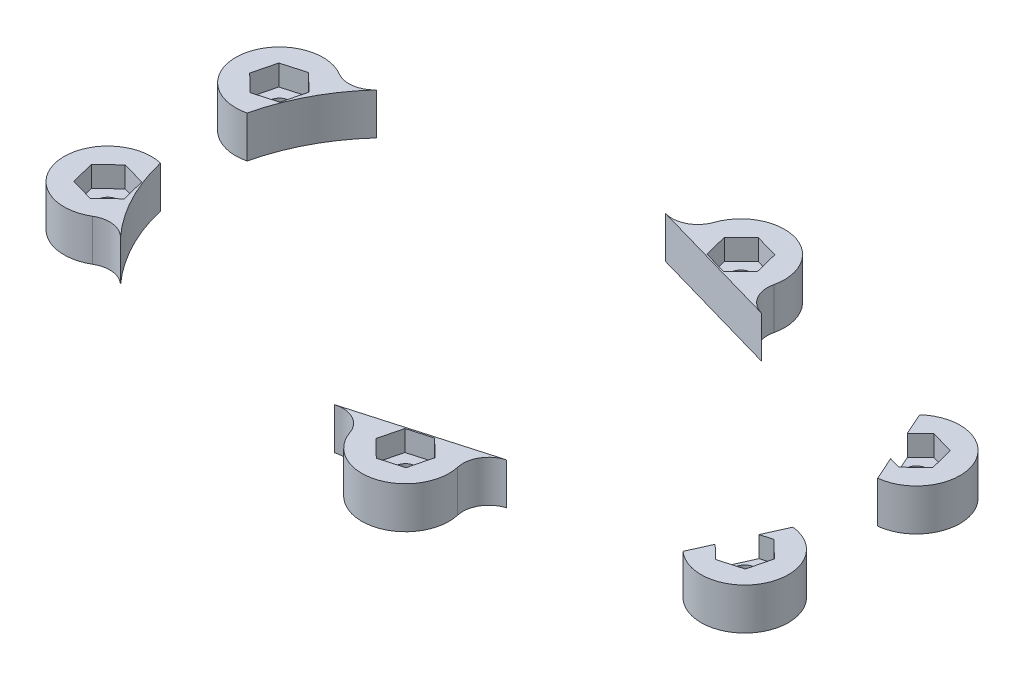
SolidWorks part; units mm, degrees
ref_plane "Front Plane" through (0, 0, 0) normal (0, 0, 1) x (1, 0, 0)
ref_plane "Top Plane" through (0, 0, 0) normal (0, 1, 0) x (1, 0, 0)
ref_plane "Right Plane" through (0, 0, 0) normal (1, 0, 0) x (0, 0, -1)
sketch "Sketch1" plane through (0, 0, 0) normal (0, 1, 0) x (1, 0, 0)
  line L0 (0, 73.0538) -> (0, -65.1274) construction
  line L1 (35.5, 6.365) -> (-28.5632, 24.502) construction
  line L2 (-70.6215, 0) -> (67.3742, 0) construction
  line L3 (35.5, -6.365) -> (-28.5632, -24.502) construction
  line L4 (4.5177, -15.1364) -> (0.1592, 0.2585)
  line L5 (0.1592, 0.2585) -> (4.6815, 1.5388)
  line L6 (4.6815, 1.5388) -> (9.04, -13.8561)
  line L7 (9.04, -13.8561) -> (9.5848, -15.7805)
  line L8 (9.5848, -15.7805) -> (5.0625, -17.0608)
  line L9 (5.0625, -17.0608) -> (4.5177, -15.1364)
  line L10 (-35.5, 0) -> (-60.5, 0) construction
  line L11 (-35.5, 0) -> (-35.5, 25) construction
  line L13 (-100, -75) -> (100, -75)
  line L14 (-100, -75) -> (-100, 75)
  line L15 (-100, 75) -> (100, 75)
  line L16 (100, -75) -> (100, 75)
  line L17 (-100, -75) -> (100, 75) construction
  line L18 (-100, 75) -> (100, -75) construction
  circle A0 centre (35.5, 0) radius 6
  circle A1 centre (-35.5, 0) radius 13.5
  circle A2 centre (-35.5, 0) radius 25.465 construction
  circle A3 centre (35.5, 0) radius 6.365 construction
  circle A4 centre (-60.5, 0) radius 2
  circle A5 centre (-35.5, 25) radius 2
  circle A6 centre (-10.5, 0) radius 2
  circle A7 centre (-35.5, -25) radius 2
  circle A8 centre (35.5, 18.5) radius 2.5
  circle A9 centre (35.5, -18.5) radius 2.5
  point P35 (0, 0)
  dimension "D1" = 12
  dimension "D2" = 27
  dimension "D5" = 50.93
  dimension "D6" = 12.73
  dimension "D12" = 4
  dimension "D19" = 5
  dimension "D3" = 71
  dimension "D4" = 35.5
  dimension "D7" = 90
  dimension "D8" = 27.5
  dimension "D9" = 4.7
  dimension "D10" = 16
  dimension "D11" = 2
  dimension "D13" = 25
  dimension "D15" = 90
  dimension "D16" = 25
  dimension "D17" = 200
  dimension "D18" = 150
  dimension "D20" = 18.5
  dimension "D14" = 4
extrude "Boss-Extrude1" add sketch "Sketch1" along normal blind 4
sketch "Sketch3" plane through (0, 4, 0) normal (0, 1, 0) x (1, 0, 0)
  line L0 (-26.5739, 31.2502) -> (39.0704, 12.5001)
  line L1 (-100, -75) -> (100, -75)
  line L2 (-100, -75) -> (-100, 75)
  line L3 (-100, 75) -> (100, 75)
  line L4 (100, -75) -> (100, 75)
  line L5 (-35.5, 0) -> (35.5, 0) construction
  line L6 (-26.5739, -31.2502) -> (39.0704, -12.5001)
  arc A0 (-26.5739, 31.2502) -> (-26.5739, -31.2502) centre (-35.5, 0) ccw
  arc A1 (39.0704, -12.5001) -> (39.0704, 12.5001) centre (35.5, 0) ccw
  dimension "D1" = 65
  dimension "D2" = 26
extrude "Boss-Extrude2" add sketch "Sketch3" along normal blind 8.25
sketch "Sketch6" plane through (0, 12.25, 0) normal (0, 1, 0) x (1, 0, 0)
  circle A0 centre (35.5, 18.5) radius 5.4
  circle A1 centre (35.5, -18.5) radius 5.4
  dimension "D1" = 10.8
extrude "Cut-Extrude2" cut sketch "Sketch6" against normal up to surface (8.25 mm away) up to face at (-35.5, 4, 27)
fillet "Fillet1" radius 2.5 4 edges at (9.5848, 2, 15.7805) (5.0625, 2, 17.0608) (4.6815, 2, -1.5388) (0.1592, 2, -0.2585)
fillet "Fillet2" radius 5 4 edges at (36.5847, 8.125, 13.2101) (31.7849, 8.125, 14.5811) (36.5847, 8.125, -13.2101) (31.7849, 8.125, -14.5811)
sketch "Sketch2" plane through (0, 4, 0) normal (0, 1, 0) x (1, 0, 0)
  line L0 (29.5, 0) -> (41.5, 0) construction
  line L1 (35.5, 0) -> (35.5, -6) construction
  line L2 (35.5, 0) -> (35.5, 6) construction
  circle A0 centre (-35.5, 25) radius 4.4
  circle A1 centre (-10.5, 0) radius 4.4
  circle A2 centre (-35.5, -25) radius 4.4
  circle A3 centre (-60.5, 0) radius 4.4
  circle A4 centre (35.5, 0) radius 6 construction
  circle A7 centre (35.5, 18.5) radius 5.4
  circle A8 centre (35.5, -18.5) radius 5.4
  arc A9 (40.6003, 16.7261) -> (30.3389, 20.0883) centre (35.5, 18.5) ccw construction
  dimension "D1" = 8.8
extrude "Cut-Extrude1" cut sketch "Sketch2" against normal blind 2
sketch "Sketch8" plane through (0, 0, 0) normal (0, -1, 0) x (1, 0, 0)
  line L0 (-35.5, 0) -> (-100, 0) construction
  line L1 (-100, -75) -> (-100, 75) construction
  line L2 (-35.5, 0) -> (100, 0) construction
  line L3 (100, 75) -> (100, -75) construction
  line L4 (49.5, 21.4955) -> (49.5, -20.5045) construction
  line L5 (0, 32.8542) -> (0, -34.16) construction
  line L6 (-73, 27.0496) -> (-73, -26.9504) construction
  line L11 (-26.5739, -31.2502) -> (24.1868, -16.7513)
  line L12 (24.1868, 16.7513) -> (-26.5739, 31.2502)
  line L13 (-26.5739, -31.2502) -> (24.1868, -16.7513) construction
  line L14 (24.1868, 16.7513) -> (-26.5739, 31.2502) construction
  circle A0 centre (-35.5, 0) radius 32.5 construction
  arc A1 (-26.5739, 31.2502) -> (-26.5739, -31.2502) centre (-35.5, 0) ccw construction
  circle A13 centre (49.5, 16.5) radius 2
  circle A14 centre (-73, 16.5) radius 2
  circle A15 centre (0, 32.25) radius 2
  circle A16 centre (49.5, 16.5) radius 4.4 construction
  circle A17 centre (0, 32.25) radius 4.4 construction
  circle A18 centre (-73, 16.5) radius 4.4 construction
  circle A19 centre (35.5, 18.5) radius 5.4 construction
  arc A20 (40.6003, 16.7261) -> (30.3389, 20.0883) centre (35.5, 18.5) ccw construction
  circle A21 centre (35.5, -18.5) radius 5.4 construction
  circle A22 centre (-73, -16.5) radius 4.4 construction
  circle A23 centre (-73, -16.5) radius 2
  circle A24 centre (0, -32.25) radius 4.4 construction
  circle A25 centre (0, -32.25) radius 2
  circle A26 centre (49.5, -16.5) radius 4.4 construction
  circle A27 centre (49.5, -16.5) radius 2
  circle A28 centre (49.5, 16.5) radius 8.4 construction
  circle A29 centre (0, 32.25) radius 8.4 construction
  circle A30 centre (-73, 16.5) radius 8.4 construction
  arc A44 (30.3389, -20.0883) -> (40.6003, -16.7261) centre (35.5, -18.5) ccw
  arc A45 (42.5943, -10.8936) -> (40.6003, -16.7261) centre (45.3228, -15.0835) ccw
  arc A46 (42.5943, -10.8936) -> (42.5943, 10.8936) centre (35.5, 0) ccw
  arc A47 (40.6003, 16.7261) -> (42.5943, 10.8936) centre (45.3228, 15.0835) ccw
  arc A48 (30.3389, -20.0883) -> (24.1868, -16.7513) centre (25.5601, -21.559) ccw
  arc A49 (40.6003, 16.7261) -> (30.3389, 20.0883) centre (35.5, 18.5) ccw
  arc A50 (24.1868, 16.7513) -> (30.3389, 20.0883) centre (25.5601, 21.559) ccw
  arc A51 (-26.5739, 31.2502) -> (-26.5739, -31.2502) centre (-35.5, 0) ccw
  arc A52 (30.3389, -20.0883) -> (40.6003, -16.7261) centre (35.5, -18.5) ccw construction
  arc A53 (42.5943, -10.8936) -> (40.6003, -16.7261) centre (45.3228, -15.0835) ccw construction
  arc A54 (42.5943, -10.8936) -> (42.5943, 10.8936) centre (35.5, 0) ccw construction
  arc A55 (40.6003, 16.7261) -> (42.5943, 10.8936) centre (45.3228, 15.0835) ccw construction
  arc A56 (30.3389, -20.0883) -> (24.1868, -16.7513) centre (25.5601, -21.559) ccw construction
  arc A57 (40.6003, 16.7261) -> (30.3389, 20.0883) centre (35.5, 18.5) ccw construction
  arc A58 (24.1868, 16.7513) -> (30.3389, 20.0883) centre (25.5601, 21.559) ccw construction
  arc A59 (-26.5739, 31.2502) -> (-26.5739, -31.2502) centre (-35.5, 0) ccw construction
  dimension "D1" = 0
  dimension "D2" = 4
  dimension "D4" = 33
  dimension "D5" = 49.5
  dimension "D3" = 8.8
  dimension "D8" = 16.8
  dimension "D6" = 64.5
  dimension "D7" = 73
extrude "Cut-Extrude3" cut sketch "Sketch8" against normal through all both and the other way through all
sketch "Sketch13" plane through (0, 12.25, 0) normal (0, 1, 0) x (1, 0, 0)
  line L0 (-100, 0) -> (100, 0) construction
  line L1 (-100, 75) -> (-100, -75) construction
  line L2 (100, -75) -> (100, 75) construction
  line L5 (-8.1313, 30.1424) -> (-25.4754, 35.0964)
  line L6 (5.7914, -26.1656) -> (25.2854, -20.5975)
  line L7 (-25.4754, -35.0964) -> (25.2854, -20.5975)
  line L8 (25.2854, 20.5975) -> (-25.4754, 35.0964)
  line L9 (-25.4754, -35.0964) -> (-8.1313, -30.1424)
  line L10 (25.2854, 20.5975) -> (5.7914, 26.1656)
  arc A0 (5.7914, 26.1656) -> (-8.1313, 30.1424) centre (0, 32.25) ccw
  arc A1 (50.4188, 8.1504) -> (43.8854, 22.7479) centre (49.5, 16.5) ccw
  arc A2 (-65.6518, 20.5699) -> (-71.0361, 8.3328) centre (-73, 16.5) ccw
  arc A3 (-65.6518, -20.5699) -> (-71.0361, -8.3328) centre (-73, -16.5) cw
  arc A4 (5.7914, -26.1656) -> (-8.1313, -30.1424) centre (0, -32.25) cw
  arc A5 (50.4188, -8.1504) -> (43.8854, -22.7479) centre (49.5, -16.5) cw
  arc A14 (-71.0361, 8.3328) -> (-71.0361, -8.3328) centre (-35.5, 0) ccw
  arc A15 (-65.6518, -20.5699) -> (-25.4754, -35.0964) centre (-35.5, 0) ccw
  arc A22 (44.3783, 15.412) -> (26.5158, 21.2649) centre (35.5, 18.5) ccw
  arc A23 (44.3783, 15.412) -> (44.7771, 14.2455) centre (45.3228, 15.0835) ccw
  arc A24 (44.7771, -14.2455) -> (44.7771, 14.2455) centre (35.5, 0) ccw
  arc A25 (44.7771, -14.2455) -> (44.3783, -15.412) centre (45.3228, -15.0835) ccw
  arc A26 (26.5158, -21.2649) -> (44.3783, -15.412) centre (35.5, -18.5) ccw
  arc A27 (26.5158, -21.2649) -> (25.2854, -20.5975) centre (25.5601, -21.559) ccw
  arc A28 (-25.4754, 35.0964) -> (-25.4754, -35.0964) centre (-35.5, 0) ccw
  arc A29 (25.2854, 20.5975) -> (26.5158, 21.2649) centre (25.5601, 21.559) ccw
  arc A30 (43.8854, 22.7479) -> (26.5158, 21.2649) centre (35.5, 18.5) ccw
  arc A32 (50.4188, -8.1504) -> (50.4188, 8.1504) centre (35.5, 0) ccw
  arc A34 (26.5158, -21.2649) -> (43.8854, -22.7479) centre (35.5, -18.5) ccw
  arc A35 (26.5158, -21.2649) -> (25.2854, -20.5975) centre (25.5601, -21.559) ccw
  arc A36 (-25.4754, 35.0964) -> (-65.6518, 20.5699) centre (-35.5, 0) ccw
  arc A37 (25.2854, 20.5975) -> (26.5158, 21.2649) centre (25.5601, 21.559) ccw
  dimension "D1" = 16.8
  dimension "D2" = 4
extrude "Cut-Extrude6" cut sketch "Sketch13" against normal through all both and the other way through all flip side to cut
fillet "Fillet4" radius 5 6 edges at (-65.6518, 6.125, 20.5699) (-65.6518, 6.125, -20.5699) (-8.1313, 6.125, -30.1424) (5.7914, 6.125, -26.1656) (5.7914, 6.125, 26.1656) (-8.1313, 6.125, 30.1424)
sketch "Sketch16" plane through (0, 12.25, 0) normal (0, 1, 0) x (1, 0, 0)
  line L12 (-25.4754, -35.0964) -> (-14.035, -31.8287)
  line L13 (11.6951, -24.4793) -> (25.2854, -20.5975)
  line L14 (25.2854, 20.5975) -> (11.6951, 24.4793)
  line L15 (-14.035, 31.8287) -> (-25.4754, 35.0964)
  line L16 (-25.4754, -35.0964) -> (-14.035, -31.8287)
  line L17 (11.6951, -24.4793) -> (25.2854, -20.5975)
  line L18 (25.2854, 20.5975) -> (11.6951, 24.4793)
  line L19 (-14.035, 31.8287) -> (-25.4754, 35.0964)
  arc A60 (-71.0361, 8.3328) -> (-71.0361, -8.3328) centre (-35.5, 0) ccw
  arc A61 (-71.0361, -8.3328) -> (-68.692, -23.7112) centre (-73, -16.5) ccw
  arc A62 (-62.4376, -24.6296) -> (-68.692, -23.7112) centre (-66.1277, -28.0035) ccw
  arc A63 (-62.4376, -24.6296) -> (-25.4754, -35.0964) centre (-35.5, 0) ccw
  arc A64 (-7.9372, -34.9997) -> (-14.035, -31.8287) centre (-12.6617, -36.6364) ccw
  arc A65 (-7.9372, -34.9997) -> (8.1921, -30.3926) centre (0, -32.25) ccw
  arc A66 (11.6951, -24.4793) -> (8.1921, -30.3926) centre (13.0683, -29.2871) ccw
  arc A67 (26.5158, -21.2649) -> (25.2854, -20.5975) centre (25.5601, -21.559) ccw
  arc A68 (26.5158, -21.2649) -> (43.8854, -22.7479) centre (35.5, -18.5) ccw
  arc A69 (43.8854, -22.7479) -> (50.4188, -8.1504) centre (49.5, -16.5) ccw
  arc A70 (50.4188, -8.1504) -> (50.4188, 8.1504) centre (35.5, 0) ccw
  arc A71 (50.4188, 8.1504) -> (43.8854, 22.7479) centre (49.5, 16.5) ccw
  arc A72 (43.8854, 22.7479) -> (26.5158, 21.2649) centre (35.5, 18.5) ccw
  arc A73 (25.2854, 20.5975) -> (26.5158, 21.2649) centre (25.5601, 21.559) ccw
  arc A74 (8.1921, 30.3926) -> (11.6951, 24.4793) centre (13.0683, 29.2871) ccw
  arc A75 (8.1921, 30.3926) -> (-7.9372, 34.9997) centre (0, 32.25) ccw
  arc A76 (-14.035, 31.8287) -> (-7.9372, 34.9997) centre (-12.6617, 36.6364) ccw
  arc A77 (-25.4754, 35.0964) -> (-62.4376, 24.6296) centre (-35.5, 0) ccw
  arc A78 (-68.692, 23.7112) -> (-62.4376, 24.6296) centre (-66.1277, 28.0035) ccw
  arc A79 (-68.692, 23.7112) -> (-71.0361, 8.3328) centre (-73, 16.5) ccw
  arc A80 (-71.0361, 8.3328) -> (-71.0361, -8.3328) centre (-35.5, 0) ccw
  arc A81 (-71.0361, -8.3328) -> (-68.692, -23.7112) centre (-73, -16.5) ccw
  arc A82 (-62.4376, -24.6296) -> (-68.692, -23.7112) centre (-66.1277, -28.0035) ccw
  arc A83 (-62.4376, -24.6296) -> (-25.4754, -35.0964) centre (-35.5, 0) ccw
  arc A84 (-7.9372, -34.9997) -> (-14.035, -31.8287) centre (-12.6617, -36.6364) ccw
  arc A85 (-7.9372, -34.9997) -> (8.1921, -30.3926) centre (0, -32.25) ccw
  arc A86 (11.6951, -24.4793) -> (8.1921, -30.3926) centre (13.0683, -29.2871) ccw
  arc A87 (26.5158, -21.2649) -> (25.2854, -20.5975) centre (25.5601, -21.559) ccw
  arc A88 (26.5158, -21.2649) -> (43.8854, -22.7479) centre (35.5, -18.5) ccw
  arc A89 (43.8854, -22.7479) -> (50.4188, -8.1504) centre (49.5, -16.5) ccw
  arc A90 (50.4188, -8.1504) -> (50.4188, 8.1504) centre (35.5, 0) ccw
  arc A91 (50.4188, 8.1504) -> (43.8854, 22.7479) centre (49.5, 16.5) ccw
  arc A92 (43.8854, 22.7479) -> (26.5158, 21.2649) centre (35.5, 18.5) ccw
  arc A93 (25.2854, 20.5975) -> (26.5158, 21.2649) centre (25.5601, 21.559) ccw
  arc A94 (8.1921, 30.3926) -> (11.6951, 24.4793) centre (13.0683, 29.2871) ccw
  arc A95 (8.1921, 30.3926) -> (-7.9372, 34.9997) centre (0, 32.25) ccw
  arc A96 (-14.035, 31.8287) -> (-7.9372, 34.9997) centre (-12.6617, 36.6364) ccw
  arc A97 (-25.4754, 35.0964) -> (-62.4376, 24.6296) centre (-35.5, 0) ccw
  arc A98 (-68.692, 23.7112) -> (-62.4376, 24.6296) centre (-66.1277, 28.0035) ccw
  arc A99 (-68.692, 23.7112) -> (-71.0361, 8.3328) centre (-73, 16.5) ccw
  dimension "D1" = 0
extrude "Cut-Extrude7" cut sketch "Sketch16" against normal up to surface (10.25 mm away) up to face at (-35.5, 2, -23)
sketch "Sketch17" plane through (0, 0, 0) normal (0, -1, 0) x (1, 0, 0)
  line L4 (4.3815, 14.6553) -> (0.8403, 2.1469)
  line L5 (5.3625, 0.8666) -> (8.9038, 13.375)
  line L6 (4.3815, 14.6553) -> (0.8403, 2.1469)
  line L7 (5.3625, 0.8666) -> (8.9038, 13.375)
  circle A6 centre (-10.5, 0) radius 2
  circle A7 centre (-10.5, 0) radius 2
  arc A8 (2.4216, -0.8943) -> (5.3625, 0.8666) centre (2.9571, 1.5477) ccw
  arc A9 (0.8403, 2.1469) -> (2.4216, -0.8943) centre (3.2457, 1.4659) ccw
  arc A10 (8.9038, 13.375) -> (7.3224, 16.4163) centre (6.4983, 14.056) ccw
  arc A11 (7.3224, 16.4163) -> (4.3815, 14.6553) centre (6.787, 13.9743) ccw
  arc A12 (2.4216, -0.8943) -> (5.3625, 0.8666) centre (2.9571, 1.5477) ccw
  arc A13 (0.8403, 2.1469) -> (2.4216, -0.8943) centre (3.2457, 1.4659) ccw
  arc A14 (8.9038, 13.375) -> (7.3224, 16.4163) centre (6.4983, 14.056) ccw
  arc A15 (7.3224, 16.4163) -> (4.3815, 14.6553) centre (6.787, 13.9743) ccw
  circle A17 centre (-35.5, -25) radius 2
  circle A18 centre (-35.5, -25) radius 2
  circle A20 centre (-35.5, 25) radius 2
  circle A21 centre (-35.5, 25) radius 2
  circle A23 centre (-60.5, 0) radius 2
  circle A24 centre (-60.5, 0) radius 2
  dimension "D1" = 0
  dimension "D2" = 0
  dimension "D3" = 0
  dimension "D4" = 0
  dimension "D5" = 0
extrude "Boss-Extrude3" add sketch "Sketch17" against normal up to surface (2 mm away) up to face at (35.5, 2, -16)
sketch "Sketch18" plane through (0, 2, 0) normal (0, 1, 0) x (1, 0, 0)
  line L8 (-25.4754, -35.0964) -> (-14.035, -31.8287)
  line L9 (11.6951, -24.4793) -> (25.2854, -20.5975)
  line L10 (25.2854, 20.5975) -> (11.6951, 24.4793)
  line L11 (-14.035, 31.8287) -> (-25.4754, 35.0964)
  line L12 (-25.4754, -35.0964) -> (-14.035, -31.8287)
  line L13 (11.6951, -24.4793) -> (25.2854, -20.5975)
  line L14 (25.2854, 20.5975) -> (11.6951, 24.4793)
  line L15 (-14.035, 31.8287) -> (-25.4754, 35.0964)
  circle A20 centre (-35.5, 0) radius 13.5
  circle A21 centre (0, 32.25) radius 2
  circle A22 centre (-73, 16.5) radius 2
  circle A23 centre (-73, -16.5) radius 2
  circle A24 centre (0, 32.25) radius 2 construction
  circle A25 centre (-35.5, 0) radius 13.5 construction
  circle A26 centre (0, -32.25) radius 2
  circle A27 centre (35.5, -18.5) radius 2.5
  circle A28 centre (35.5, 0) radius 6
  circle A29 centre (49.5, -16.5) radius 2
  circle A30 centre (35.5, 18.5) radius 2.5
  circle A31 centre (49.5, 16.5) radius 2
  circle A32 centre (-73, 16.5) radius 2 construction
  circle A33 centre (-73, -16.5) radius 2 construction
  circle A34 centre (0, -32.25) radius 2 construction
  circle A35 centre (35.5, -18.5) radius 2.5 construction
  circle A36 centre (35.5, 0) radius 6 construction
  circle A37 centre (35.5, 18.5) radius 2.5 construction
  circle A38 centre (49.5, 16.5) radius 2 construction
  circle A39 centre (49.5, -16.5) radius 2 construction
  arc A40 (-68.692, 23.7112) -> (-71.0361, 8.3328) centre (-73, 16.5) ccw
  arc A41 (-71.0361, 8.3328) -> (-71.0361, -8.3328) centre (-35.5, 0) ccw
  arc A42 (-71.0361, -8.3328) -> (-68.692, -23.7112) centre (-73, -16.5) ccw
  arc A43 (-62.4376, -24.6296) -> (-68.692, -23.7112) centre (-66.1277, -28.0035) ccw
  arc A44 (-62.4376, -24.6296) -> (-25.4754, -35.0964) centre (-35.5, 0) ccw
  arc A45 (-7.9372, -34.9997) -> (-14.035, -31.8287) centre (-12.6617, -36.6364) ccw
  arc A46 (-7.9372, -34.9997) -> (8.1921, -30.3926) centre (0, -32.25) ccw
  arc A47 (11.6951, -24.4793) -> (8.1921, -30.3926) centre (13.0683, -29.2871) ccw
  arc A48 (26.5158, -21.2649) -> (25.2854, -20.5975) centre (25.5601, -21.559) ccw
  arc A49 (26.5158, -21.2649) -> (43.8854, -22.7479) centre (35.5, -18.5) ccw
  arc A50 (43.8854, -22.7479) -> (50.4188, -8.1504) centre (49.5, -16.5) ccw
  arc A51 (50.4188, -8.1504) -> (50.4188, 8.1504) centre (35.5, 0) ccw
  arc A52 (50.4188, 8.1504) -> (43.8854, 22.7479) centre (49.5, 16.5) ccw
  arc A53 (43.8854, 22.7479) -> (26.5158, 21.2649) centre (35.5, 18.5) ccw
  arc A54 (25.2854, 20.5975) -> (26.5158, 21.2649) centre (25.5601, 21.559) ccw
  arc A55 (8.1921, 30.3926) -> (11.6951, 24.4793) centre (13.0683, 29.2871) ccw
  arc A56 (8.1921, 30.3926) -> (-7.9372, 34.9997) centre (0, 32.25) ccw
  arc A57 (-14.035, 31.8287) -> (-7.9372, 34.9997) centre (-12.6617, 36.6364) ccw
  arc A58 (-25.4754, 35.0964) -> (-62.4376, 24.6296) centre (-35.5, 0) ccw
  arc A59 (-68.692, 23.7112) -> (-62.4376, 24.6296) centre (-66.1277, 28.0035) ccw
  arc A60 (-68.692, 23.7112) -> (-71.0361, 8.3328) centre (-73, 16.5) ccw
  arc A61 (-71.0361, 8.3328) -> (-71.0361, -8.3328) centre (-35.5, 0) ccw
  arc A62 (-71.0361, -8.3328) -> (-68.692, -23.7112) centre (-73, -16.5) ccw
  arc A63 (-62.4376, -24.6296) -> (-68.692, -23.7112) centre (-66.1277, -28.0035) ccw
  arc A64 (-62.4376, -24.6296) -> (-25.4754, -35.0964) centre (-35.5, 0) ccw
  arc A65 (-7.9372, -34.9997) -> (-14.035, -31.8287) centre (-12.6617, -36.6364) ccw
  arc A66 (-7.9372, -34.9997) -> (8.1921, -30.3926) centre (0, -32.25) ccw
  arc A67 (11.6951, -24.4793) -> (8.1921, -30.3926) centre (13.0683, -29.2871) ccw
  arc A68 (26.5158, -21.2649) -> (25.2854, -20.5975) centre (25.5601, -21.559) ccw
  arc A69 (26.5158, -21.2649) -> (43.8854, -22.7479) centre (35.5, -18.5) ccw
  arc A70 (43.8854, -22.7479) -> (50.4188, -8.1504) centre (49.5, -16.5) ccw
  arc A71 (50.4188, -8.1504) -> (50.4188, 8.1504) centre (35.5, 0) ccw
  arc A72 (50.4188, 8.1504) -> (43.8854, 22.7479) centre (49.5, 16.5) ccw
  arc A73 (43.8854, 22.7479) -> (26.5158, 21.2649) centre (35.5, 18.5) ccw
  arc A74 (25.2854, 20.5975) -> (26.5158, 21.2649) centre (25.5601, 21.559) ccw
  arc A75 (8.1921, 30.3926) -> (11.6951, 24.4793) centre (13.0683, 29.2871) ccw
  arc A76 (8.1921, 30.3926) -> (-7.9372, 34.9997) centre (0, 32.25) ccw
  arc A77 (-14.035, 31.8287) -> (-7.9372, 34.9997) centre (-12.6617, 36.6364) ccw
  arc A78 (-25.4754, 35.0964) -> (-62.4376, 24.6296) centre (-35.5, 0) ccw
  arc A79 (-68.692, 23.7112) -> (-62.4376, 24.6296) centre (-66.1277, 28.0035) ccw
  dimension "D1" = 0
extrude "Boss-Extrude4" add sketch "Sketch18" along normal blind 6
sketch "Sketch19" plane through (0, 0, 0) normal (0, -1, 0) x (1, 0, 0)
  line L0 (25.975, 0) -> (45.025, 0) construction
  circle A0 centre (-35.5, 0) radius 19.5
  circle A1 centre (35.5, 0) radius 9.525 construction
  circle A2 centre (35.5, 9.525) radius 0.75
  circle A3 centre (35.5, -9.525) radius 0.75
  dimension "D1" = 39
  dimension "D2" = 19.05
  dimension "D3" = 1.5
extrude "Cut-Extrude8" cut sketch "Sketch19" against normal through all both and the other way through all
sketch "Sketch20" plane through (0, 0, 0) normal (0, -1, 0) x (1, 0, 0)
  line L1 (40.1188, 18.5) -> (37.8094, 22.5)
  line L2 (37.8094, 22.5) -> (33.1906, 22.5)
  line L3 (33.1906, 22.5) -> (30.8812, 18.5)
  line L4 (30.8812, 18.5) -> (33.1906, 14.5)
  line L5 (33.1906, 14.5) -> (37.8094, 14.5)
  line L6 (37.8094, 14.5) -> (40.1188, 18.5)
  line L7 (40.1188, -18.5) -> (37.8094, -14.5)
  line L8 (37.8094, -14.5) -> (33.1906, -14.5)
  line L9 (33.1906, -14.5) -> (30.8812, -18.5)
  line L10 (30.8812, -18.5) -> (33.1906, -22.5)
  line L11 (33.1906, -22.5) -> (37.8094, -22.5)
  line L12 (37.8094, -22.5) -> (40.1188, -18.5)
  circle A0 centre (35.5, 18.5) radius 4 construction
  circle A1 centre (35.5, -18.5) radius 4 construction
  dimension "D1" = 8
  dimension "D2" = 8
extrude "Cut-Extrude9" cut sketch "Sketch20" against normal blind 4
sketch "Sketch21" plane through (0, 8, 0) normal (0, 1, 0) x (1, 0, 0)
  line L0 (25.2854, 20.5975) -> (11.6951, 24.4793) construction
  line L1 (-69.6808, 13.2881) -> (-68.5588, 17.7685)
  line L2 (-68.5588, 17.7685) -> (-71.878, 20.9805)
  line L3 (-71.878, 20.9805) -> (-76.3192, 19.7119)
  line L4 (-76.3192, 19.7119) -> (-77.4412, 15.2315)
  line L5 (-77.4412, 15.2315) -> (-74.122, 12.0195)
  line L6 (-74.122, 12.0195) -> (-69.6808, 13.2881)
  line L7 (-69.6808, -13.2881) -> (-74.122, -12.0195)
  line L8 (-74.122, -12.0195) -> (-77.4412, -15.2315)
  line L9 (-77.4412, -15.2315) -> (-76.3192, -19.7119)
  line L10 (-76.3192, -19.7119) -> (-71.878, -20.9805)
  line L11 (-71.878, -20.9805) -> (-68.5588, -17.7685)
  line L12 (-68.5588, -17.7685) -> (-69.6808, -13.2881)
  line L13 (4.4412, 30.9815) -> (3.3192, 35.4619)
  line L14 (3.3192, 35.4619) -> (-1.122, 36.7305)
  line L15 (-1.122, 36.7305) -> (-4.4412, 33.5185)
  line L16 (-4.4412, 33.5185) -> (-3.3192, 29.0381)
  line L17 (-3.3192, 29.0381) -> (1.122, 27.7695)
  line L18 (1.122, 27.7695) -> (4.4412, 30.9815)
  line L19 (50.622, 12.0195) -> (53.9412, 15.2315)
  line L20 (53.9412, 15.2315) -> (52.8192, 19.7119)
  line L21 (52.8192, 19.7119) -> (48.378, 20.9805)
  line L22 (48.378, 20.9805) -> (45.0588, 17.7685)
  line L23 (45.0588, 17.7685) -> (46.1808, 13.2881)
  line L24 (46.1808, 13.2881) -> (50.622, 12.0195)
  line L25 (53.9412, -15.2315) -> (50.622, -12.0195)
  line L26 (50.622, -12.0195) -> (46.1808, -13.2881)
  line L27 (46.1808, -13.2881) -> (45.0588, -17.7685)
  line L28 (45.0588, -17.7685) -> (48.378, -20.9805)
  line L29 (48.378, -20.9805) -> (52.8192, -19.7119)
  line L30 (52.8192, -19.7119) -> (53.9412, -15.2315)
  line L31 (4.4412, -30.9815) -> (1.122, -27.7695)
  line L32 (1.122, -27.7695) -> (-3.3192, -29.0381)
  line L33 (-3.3192, -29.0381) -> (-4.4412, -33.5185)
  line L34 (-4.4412, -33.5185) -> (-1.122, -36.7305)
  line L35 (-1.122, -36.7305) -> (3.3192, -35.4619)
  line L36 (3.3192, -35.4619) -> (4.4412, -30.9815)
  line L37 (11.6951, -24.4793) -> (25.2854, -20.5975) construction
  line L38 (-25.4754, -35.0964) -> (-14.035, -31.8287) construction
  line L39 (-14.035, 31.8287) -> (-25.4754, 35.0964) construction
  circle A0 centre (-73, 16.5) radius 4 construction
  circle A1 centre (-73, -16.5) radius 4 construction
  circle A2 centre (0, 32.25) radius 4 construction
  circle A3 centre (49.5, 16.5) radius 4 construction
  circle A4 centre (49.5, -16.5) radius 4 construction
  circle A5 centre (0, -32.25) radius 4 construction
  point P46 (-70.2184, -19.3745)
  dimension "D1" = 8
  dimension "D2" = 8
  dimension "D3" = 8
  dimension "D4" = 8
  dimension "D5" = 8
  dimension "D6" = 8
extrude "Cut-Extrude10" cut sketch "Sketch21" against normal blind 4
sketch "Sketch22" plane through (0, 0, 0) normal (0, -1, 0) x (1, 0, 0)
  line L0 (-14.035, 31.8287) -> (11.6951, 24.4793)
  line L1 (-14.035, -31.8287) -> (11.6951, -24.4793)
  line L2 (43.8854, 22.7479) -> (50.4188, 8.1504)
  line L3 (50.4188, -8.1504) -> (43.8854, -22.7479)
  arc A0 (-14.035, 31.8287) -> (-7.9372, 34.9997) centre (-12.6617, 36.6364) ccw construction
  arc A1 (8.1921, 30.3926) -> (-7.9372, 34.9997) centre (0, 32.25) ccw construction
  arc A2 (8.1921, 30.3926) -> (11.6951, 24.4793) centre (13.0683, 29.2871) ccw construction
  arc A3 (8.1921, 30.3926) -> (11.6951, 24.4793) centre (13.0683, 29.2871) ccw
  arc A4 (8.1921, 30.3926) -> (-7.9372, 34.9997) centre (0, 32.25) ccw
  arc A5 (-14.035, 31.8287) -> (-7.9372, 34.9997) centre (-12.6617, 36.6364) ccw
  arc A6 (11.6951, -24.4793) -> (8.1921, -30.3926) centre (13.0683, -29.2871) ccw construction
  arc A7 (-7.9372, -34.9997) -> (8.1921, -30.3926) centre (0, -32.25) ccw construction
  arc A8 (-7.9372, -34.9997) -> (-14.035, -31.8287) centre (-12.6617, -36.6364) ccw construction
  arc A9 (-7.9372, -34.9997) -> (-14.035, -31.8287) centre (-12.6617, -36.6364) ccw
  arc A10 (-7.9372, -34.9997) -> (8.1921, -30.3926) centre (0, -32.25) ccw
  arc A11 (11.6951, -24.4793) -> (8.1921, -30.3926) centre (13.0683, -29.2871) ccw
  arc A12 (-62.4376, 24.6296) -> (-71.0361, 8.3328) centre (-35.5, 0) ccw
  arc A13 (-68.692, 23.7112) -> (-71.0361, 8.3328) centre (-73, 16.5) ccw construction
  arc A14 (-68.692, 23.7112) -> (-62.4376, 24.6296) centre (-66.1277, 28.0035) ccw construction
  arc A15 (-68.692, 23.7112) -> (-71.0361, 8.3328) centre (-73, 16.5) ccw
  arc A16 (-68.692, 23.7112) -> (-62.4376, 24.6296) centre (-66.1277, 28.0035) ccw
  arc A17 (-71.0361, -8.3328) -> (-62.4376, -24.6296) centre (-35.5, 0) ccw
  arc A19 (-71.0361, -8.3328) -> (-68.692, -23.7112) centre (-73, -16.5) ccw construction
  arc A20 (-62.4376, -24.6296) -> (-68.692, -23.7112) centre (-66.1277, -28.0035) ccw construction
  arc A21 (-62.4376, -24.6296) -> (-68.692, -23.7112) centre (-66.1277, -28.0035) ccw
  arc A22 (-71.0361, -8.3328) -> (-68.692, -23.7112) centre (-73, -16.5) ccw
  arc A23 (50.4188, 8.1504) -> (43.8854, 22.7479) centre (49.5, 16.5) ccw construction
  arc A24 (50.4188, 8.1504) -> (43.8854, 22.7479) centre (49.5, 16.5) ccw
  arc A25 (43.8854, -22.7479) -> (50.4188, -8.1504) centre (49.5, -16.5) ccw construction
  arc A26 (43.8854, -22.7479) -> (50.4188, -8.1504) centre (49.5, -16.5) ccw
extrude "Cut-Extrude12" cut sketch "Sketch22" against normal blind 10 flip side to cut
